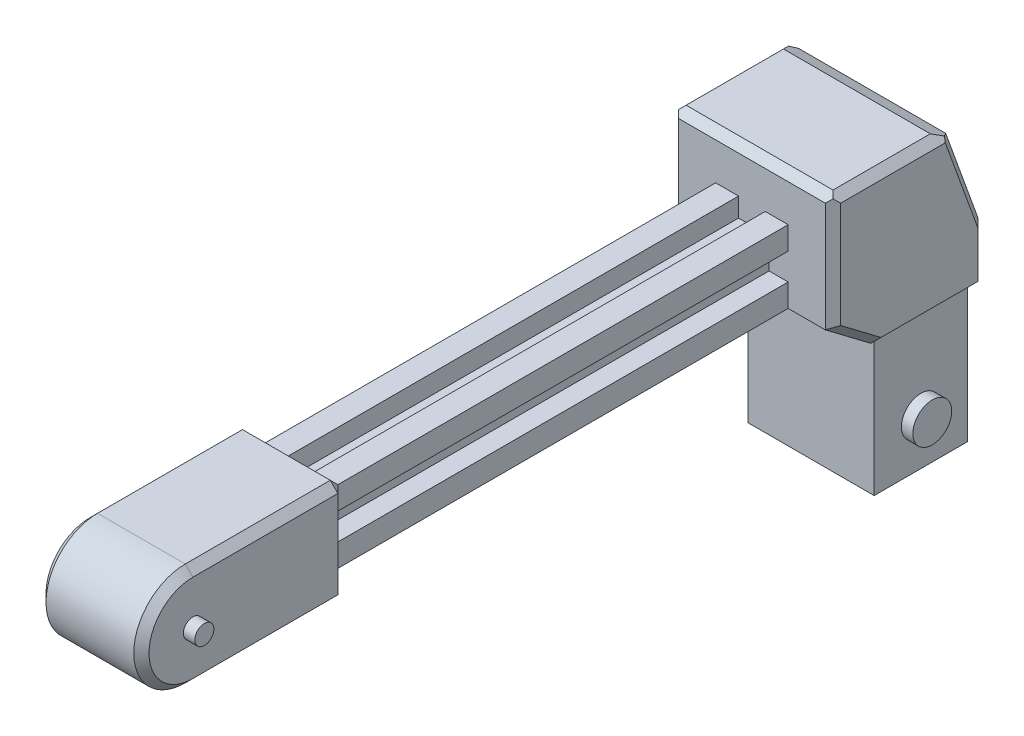
SolidWorks part; units mm, degrees
note: '?' marks a value the reader was unsure of.
ref_plane "前视基准面" through (0, 0, 0) normal (0, 0, 1) x (1, 0, 0)
ref_plane "上视基准面" through (0, 0, 0) normal (0, 1, 0) x (1, 0, 0)
ref_plane "右视基准面" through (0, 0, 0) normal (1, 0, 0) x (0, 0, -1)
sketch "草图1" plane through (0, 0, 0) normal (1, 0, 0) x (0, 0, -1)
  line L1 (0, 0) -> (200, 0)
  line L2 (0, 0) -> (0, 19)
  line L3 (0, 19) -> (200, 19)
  line L4 (200, 0) -> (200, 19)
  dimension "D1" = 200
  dimension "D2" = 19
extrude "凸台-拉伸1" add sketch "草图1" along normal blind 19
sketch "草图2" plane through (19, 0, 0) normal (1, 0, 0) x (0, 0, -1)
  line L0 (0, 19) -> (0, 0) construction
  line L1 (0, 19) -> (0, 0)
  arc A0 (0, 19) -> (0, 0) centre (0, 9.5) ccw
sketch "草图6" plane through (0, 0, 0) normal (0, 0, 1) x (1, 0, 0)
  line L0 (0, 9.5) -> (19, 9.5) construction
  line L1 (0, 19) -> (0, 0) construction
  line L2 (19, 0) -> (19, 19) construction
  line L3 (9.5, 19) -> (9.5, 0) construction
  line L4 (19, 19) -> (0, 19) construction
  line L5 (19, 0) -> (0, 0) construction
  line L7 (-4, -4) -> (23, -4)
  line L8 (-4, -4) -> (-4, 23)
  line L9 (-4, 23) -> (23, 23)
  line L10 (23, -4) -> (23, 23)
  line L11 (-4, -4) -> (23, 23) construction
  line L12 (-4, 23) -> (23, -4) construction
  point P12 (9.5, 9.5)
  dimension "D1" = 27
  dimension "D2" = 27
extrude "凸台-拉伸6" add sketch "草图6" against normal blind 40
sketch "草图7" plane through (23, 0, 0) normal (1, 0, 0) x (0, 0, -1)
  line L0 (0, 19) -> (0, 0) construction
  line L1 (0, -4) -> (0, 23)
  arc A0 (0, 23) -> (0, -4) centre (0, 9.5) ccw
extrude "凸台-拉伸7" add sketch "草图7" against normal up to surface (27 mm away) up to face at (-4, 9.5, -20)
sketch "草图8" plane through (0, 0, -200) normal (0, 0, -1) x (-1, 0, 0)
  line L0 (-19, 9.5) -> (0, 9.5) construction
  line L1 (-19, 19) -> (-19, 0) construction
  line L2 (0, 19) -> (0, 0) construction
  line L3 (-9.5, 19) -> (-9.5, 0) construction
  line L4 (0, 19) -> (-19, 19) construction
  line L5 (-19, 0) -> (0, 0) construction
  line L7 (-30.75, -11.75) -> (11.75, -11.75)
  line L8 (-30.75, -11.75) -> (-30.75, 30.75)
  line L9 (-30.75, 30.75) -> (11.75, 30.75)
  line L10 (11.75, -11.75) -> (11.75, 30.75)
  line L11 (-30.75, -11.75) -> (11.75, 30.75) construction
  line L12 (-30.75, 30.75) -> (11.75, -11.75) construction
  point P12 (-9.5, 9.5)
  dimension "D1" = 42.5
  dimension "D2" = 42.5
extrude "凸台-拉伸8" add sketch "草图8" against normal blind 40
sketch "草图9" plane through (23, 0, 0) normal (1, 0, 0) x (0, 0, -1)
  line L0 (0, 19) -> (0, 0) construction
  circle A0 centre (0, 9.5) radius 2.5
  dimension "D1" = 5
extrude "凸台-拉伸9" add sketch "草图9" along normal blind 3
sketch "草图10" plane through (-4, 0, 0) normal (-1, 0, 0) x (0, 0, 1)
  line L0 (0, 19) -> (0, 0) construction
  circle A0 centre (0, 9.5) radius 2.5
  dimension "D1" = 5
extrude "凸台-拉伸10" add sketch "草图10" along normal blind 3
sketch "草图11" plane through (0, -11.75, 0) normal (0, -1, 0) x (1, 0, 0)
  line L0 (30.75, -200) -> (-11.75, -200) construction
  line L1 (26, -200) -> (-7, -200)
  line L2 (26, -200) -> (26, -175.5383)
  line L3 (26, -175.5383) -> (-7, -175.5383)
  line L4 (-7, -200) -> (-7, -175.5383)
  line L5 (9.5, -175.5383) -> (9.5, -200) construction
  line L6 (9.5, -160) -> (9.5, -200) construction
  line L7 (0, -160) -> (19, -160) construction
  dimension "D1" = 33
extrude "凸台-拉伸11" add sketch "草图11" along normal blind 35
sketch "草图12" plane through (30.75, 0, 0) normal (1, 0, 0) x (0, 0, -1)
  line L0 (160, 0) -> (175.5383, -11.75)
  line L1 (160, -11.75) -> (200, -11.75) construction
  line L2 (175.5383, -46.75) -> (175.5383, -11.75) construction
  line L3 (175.5383, -11.75) -> (160, -11.75)
  line L4 (160, -11.75) -> (160, 0)
extrude "切除-拉伸1" cut sketch "草图12" against normal up to surface (42.5 mm away) up to face at (-11.75, 9.5, -180)
sketch "草图13" plane through (-11.75, 0, 0) normal (-1, 0, 0) x (0, 0, 1)
  line L0 (-190.8391, 30.75) -> (-200, 5.411)
  line L1 (-160, 30.75) -> (-200, 30.75) construction
  line L2 (-200, -11.75) -> (-200, 30.75) construction
  line L3 (-200, 5.411) -> (-200, 30.75)
  line L4 (-200, 30.75) -> (-190.8391, 30.75)
extrude "切除-拉伸2" cut sketch "草图13" against normal up to surface (42.5 mm away) up to face at (30.75, 7.6, -179.1077)
sketch "草图14" plane through (0, 0, -200) normal (0, 0, -1) x (-1, 0, 0)
  line L0 (-26, -11.75) -> (-30.75, -7)
  line L1 (-30.75, 5.411) -> (-30.75, -11.75) construction
  line L2 (-30.75, -7) -> (-30.75, -11.75)
  line L3 (-30.75, -11.75) -> (-26, -11.75)
  line L4 (7, -11.75) -> (11.75, -7)
  line L5 (11.75, -11.75) -> (11.75, 5.411) construction
  line L6 (11.75, -7) -> (11.75, -11.75)
  line L7 (7, -11.75) -> (11.75, -11.75) construction
  line L8 (11.75, -11.75) -> (7, -11.75)
  dimension "D1" = 45
  dimension "D2" = 45
extrude "切除-拉伸3" cut sketch "草图14" against normal up to surface (30.7431 mm away) up to face at (9.5, -5.875, -167.7691)
sketch "草图15" plane through (0, 0, 0) normal (-1, 0, 0) x (0, 0, 1)
  line L0 (-160, 9.5) -> (-40, 9.5) construction
  line L1 (-160, 0) -> (-160, 19) construction
  line L2 (-40, 23) -> (-40, -4) construction
  line L3 (-40, 19) -> (-40, 0) construction
  line L4 (-40, 13) -> (-160, 13)
  line L5 (-40, 13) -> (-40, 6)
  line L6 (-40, 6) -> (-160, 6)
  line L7 (-160, 13) -> (-160, 6)
  line L8 (-40, 9.5) -> (-160, 9.5) construction
  dimension "D1" = 7
extrude "切除-拉伸4" cut sketch "草图15" against normal blind 5
sketch "草图16" plane through (19, 0, 0) normal (1, 0, 0) x (0, 0, -1)
  line L0 (40, -4) -> (40, 23) construction
  line L1 (40, 13) -> (160, 13)
  line L2 (40, 13) -> (40, 6)
  line L3 (40, 6) -> (160, 6)
  line L4 (160, 13) -> (160, 6)
  line L5 (160, 30.75) -> (160, 0) construction
  line L6 (40, 9.5) -> (110.7117, 9.5)
  line L7 (40, 9.5) -> (101.9301, 9.5)
  line L8 (40, 19) -> (40, 0) construction
  dimension "D1" = 7
extrude "切除-拉伸5" cut sketch "草图16" against normal blind 5
sketch "草图17" plane through (0, 0, 0) normal (0, -1, 0) x (1, 0, 0)
  line L0 (19, -40) -> (0, -40) construction
  line L1 (6, -40) -> (13, -40)
  line L2 (6, -40) -> (6, -160)
  line L3 (6, -160) -> (13, -160)
  line L4 (13, -40) -> (13, -160)
  line L5 (0, -160) -> (19, -160) construction
  line L6 (9.5, -40) -> (9.5, -77.3026)
  line L7 (9.5, -160) -> (9.5, -109.9423)
  dimension "D1" = 7
extrude "切除-拉伸6" cut sketch "草图17" against normal blind 5
sketch "草图18" plane through (0, 19, 0) normal (0, 1, 0) x (1, 0, 0)
  line L0 (-11.75, 160) -> (30.75, 160) construction
  line L1 (6, 160) -> (13, 160)
  line L2 (6, 160) -> (6, 40)
  line L3 (6, 40) -> (13, 40)
  line L4 (13, 160) -> (13, 40)
  line L5 (0, 40) -> (19, 40) construction
  line L6 (9.5, 40) -> (9.5, 44.0403)
  line L7 (9.5, 40) -> (9.5, 49.1059)
  line L8 (9.5, 40) -> (9.5, 47.2552) construction
  dimension "D1" = 7
extrude "切除-拉伸7" cut sketch "草图18" against normal blind 5
chamfer "倒角1" distance 2 angle 45 5 edges at (30.75, -0.7945, -200) (30.75, 18.0805, -195.4196) (30.75, 30.75, -175.4196) (30.75, -3.5, -164.6284) (30.75, 15.375, -160)
chamfer "倒角2" distance 2 angle 45 5 edges at (-11.75, -0.7945, -200) (-11.75, -3.5, -164.6284) (-11.75, 15.375, -160) (-11.75, 30.75, -175.4196) (-11.75, 18.0805, -195.4196)
chamfer "倒角3" distance 2 angle 45 2 edges at (9.5, 30.75, -190.8391) (9.5, 30.75, -160) first distance on face at (9.5, 18.0805, -195.4196) first distance on face at (9.5, 12.075, -160)
chamfer "倒角4" distance 2 angle 45 10 edges at (-4, -4, -20) (23, -4, -20) (-4, 9.5, 13.5) (23, 9.5, 13.5) (23, 9.5, -40) (9.5, -4, -40) (-4, 9.5, -40) (-4, 23, -20) (9.5, 23, -40) (23, 23, -20)
sketch "Sketch2" plane through (-7, 0, 0) normal (-1, 0, 0) x (0, 0, 1)
  line L5 (-200, -46.75) -> (-175.5383, -46.75) construction
  arc A4 (-183.0691, -32.7701) -> (-192.4691, -32.7701) centre (-187.7691, -34.75) cw
  circle A5 centre (-187.7691, -34.75) radius 5.1
  point P15 (-187.7691, -46.75)
  dimension "D2" = 5.1
  dimension "D1" = 12
extrude "Boss-Extrude1" add sketch "Sketch2" along normal blind 3 contours A4 A5
sketch "Sketch3" plane through (26, 0, 0) normal (1, 0, 0) x (0, 0, -1)
  line L0 (200, -46.75) -> (175.5383, -46.75) construction
  arc A0 (192.4691, -32.7701) -> (183.0691, -32.7701) centre (187.7691, -34.75) cw
  circle A1 centre (187.7691, -34.75) radius 5.1
  point P6 (187.7691, -46.75)
  dimension "D1" = 10.2
  dimension "D2" = 12
extrude "Boss-Extrude2" add sketch "Sketch3" along normal blind 3 contours A0 A1
ref_axis "Axis1" through (-2, 9.5, 0) along (1, 0, 0)?
ref_plane "Plane2" through (9.5, 0, 0) normal (1, 0, 0) x (0, 0, -1)
ref_point "Point5"
ref_axis "Axis2" through (-34.6538, -34.75, -187.7691) along (1, 0, 0)?
ref_plane "Plane3" through (9.5, 0, 0) normal (1, 0, 0) x (0, 0, -1)
ref_plane "Plane4" through (9.5, 0, 0) normal (-1, 0, 0) x (0, 0, 1)
ref_axis "Axis3" through (29, -34.75, -187.7691) along (-1, 0, 0)?
ref_point "Point6"
ref_axis "Axis4" through (9.5, 9.5, 0) along (0, -0.2294, -0.9733)?
